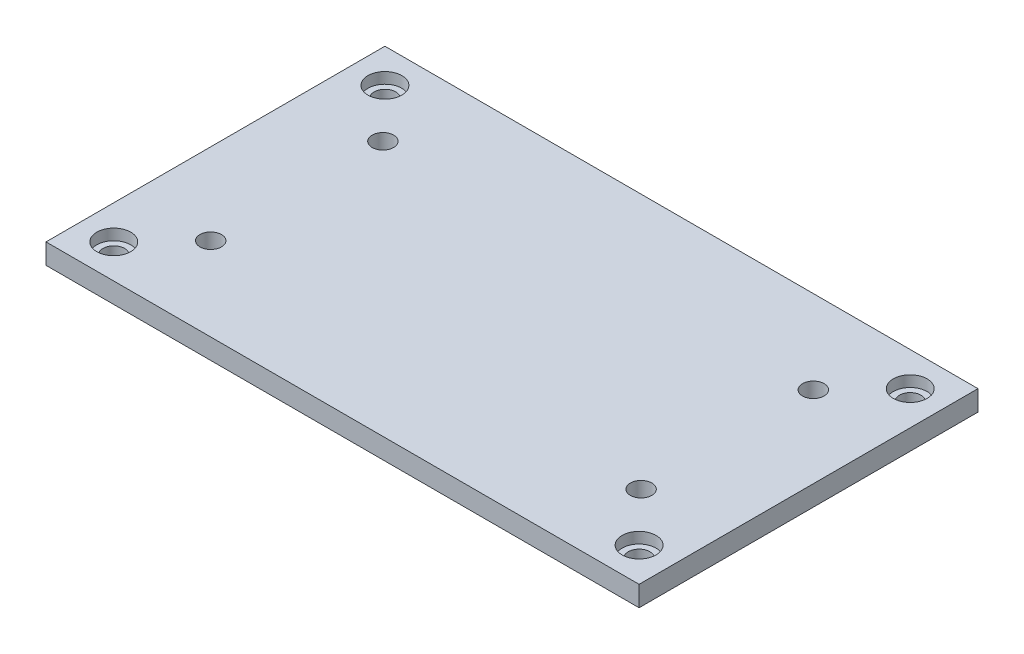
SolidWorks part; units mm, degrees
ref_plane "Front Plane" through (0, 0, 0) normal (0, 0, 1) x (1, 0, 0)
ref_plane "Top Plane" through (0, 0, 0) normal (0, 1, 0) x (1, 0, 0)
ref_plane "Right Plane" through (0, 0, 0) normal (1, 0, 0) x (0, 0, -1)
sketch "Sketch1" plane through (0, 0, 0) normal (0, 1, 0) x (1, 0, 0)
  line L0 (-55, 0) -> (55, 0) construction
  line L1 (-87.5, 50) -> (87.5, 50)
  line L2 (-87.5, 50) -> (-87.5, -50)
  line L3 (-87.5, -50) -> (87.5, -50)
  line L4 (87.5, 50) -> (87.5, -50)
  line L5 (-87.5, 50) -> (87.5, -50) construction
  line L6 (-87.5, -50) -> (87.5, 50) construction
  line L7 (0, -55) -> (0, 55) construction
  circle A0 centre (-77.5, -40) radius 3.175
  circle A1 centre (-77.5, 40) radius 3.175
  circle A2 centre (77.5, 40) radius 3.175
  circle A3 centre (77.5, -40) radius 3.175
  circle A4 centre (-63.5, 25.4) radius 3.175
  circle A5 centre (-63.5, -25.4) radius 3.175
  circle A6 centre (63.5, -25.4) radius 3.175
  circle A7 centre (63.5, 25.4) radius 3.175
  point P0 (0, 0)
  point P26 (-76.5829, 25.4)
  point P27 (0, 0)
  dimension "D3" = 6.35
  dimension "D1" = 100
  dimension "D2" = 175
  dimension "D4" = 40
  dimension "D5" = 77.5
  dimension "D6" = 25.4
  dimension "D7" = 63.5
extrude "Boss-Extrude1" add sketch "Sketch1" along normal blind 6
sketch "Sketch2" plane through (0, 6, 0) normal (0, 1, 0) x (1, 0, 0)
  line L0 (-3.3, 0) -> (3.3, 0) construction
  line L1 (0, -3.3) -> (0, 3.3) construction
  circle A0 centre (-77.5, 40) radius 5
  circle A1 centre (-77.5, -40) radius 5
  circle A2 centre (77.5, -40) radius 5
  circle A3 centre (77.5, 40) radius 5
  dimension "D1" = 10
extrude "Cut-Extrude1" cut sketch "Sketch2" against normal blind 3.25
